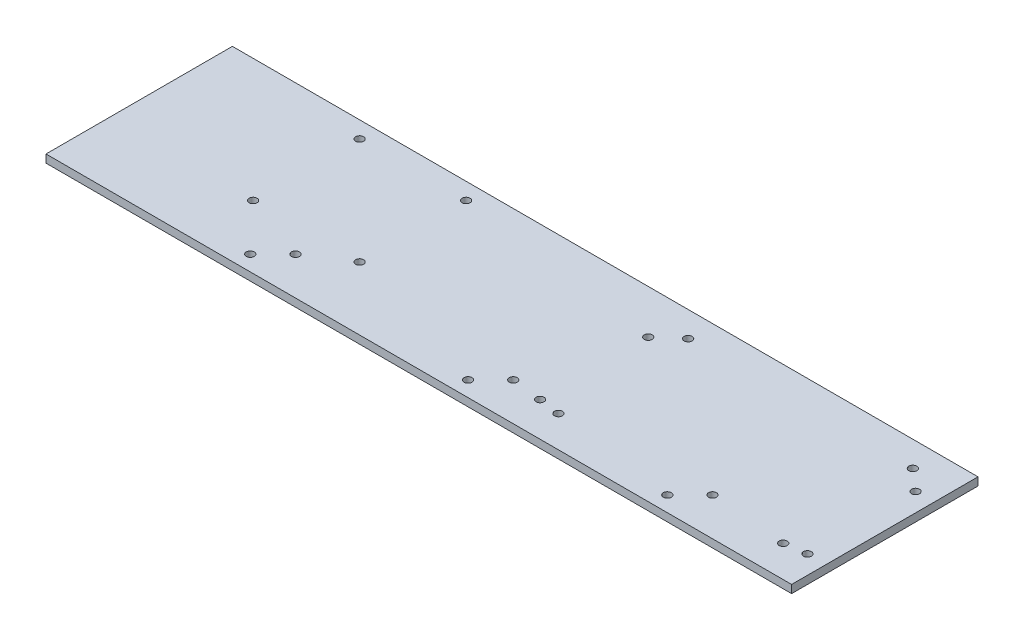
SolidWorks part; units mm, degrees
ref_plane "Front Plane" through (0, 0, 0) normal (0, 0, 1) x (1, 0, 0)
ref_plane "Top Plane" through (0, 0, 0) normal (0, 1, 0) x (1, 0, 0)
ref_plane "Right Plane" through (0, 0, 0) normal (1, 0, 0) x (0, 0, -1)
sketch "Sketch1" plane through (0, 0, 0) normal (0, 1, 0) x (1, 0, 0)
  line L1 (-140, -35) -> (140, -35)
  line L2 (-140, -35) -> (-140, 35)
  line L3 (-140, 35) -> (140, 35)
  line L4 (140, -35) -> (140, 35)
  line L5 (-140, -35) -> (140, 35) construction
  line L6 (-140, 35) -> (140, -35) construction
  circle A1 centre (87.5712, -29.2426) radius 1.5
  circle A2 centre (96.0565, -20.7574) radius 1.5
  circle A6 centre (133.0434, 18.5) radius 1.5 construction
  circle A9 centre (32.6434, 18.5) radius 1.5
  circle A10 centre (12.7294, -29.2426) radius 1.5
  circle A11 centre (21.2147, -20.7574) radius 1.5
  circle A12 centre (-60.5678, -20.7574) radius 1.5
  circle A13 centre (-69.0531, -29.2426) radius 1.5
  circle A14 centre (40.6434, 25.5) radius 1.5
  circle A15 centre (32.6434, -22.1) radius 1.5
  circle A16 centre (40.6434, -23.2) radius 1.5
  circle A17 centre (125.0434, -23.2) radius 1.5
  circle A18 centre (133.0434, -22.1) radius 1.5
  circle A19 centre (133.0434, 18.5) radius 1.5
  circle A20 centre (125.0434, 25.5) radius 1.5
  circle A21 centre (-85.9926, 28.7487) radius 1.5
  circle A22 centre (-45.9926, 28.7487) radius 1.5
  circle A23 centre (-45.9926, -11.2513) radius 1.5
  circle A24 centre (-85.9926, -11.2513) radius 1.5
  point P0 (0, 0)
  dimension "D3" = 3
  dimension "D4" = 3
  dimension "D5" = 3
  dimension "D6" = 3
  dimension "D7" = 3
  dimension "D8" = 3
  dimension "D9" = 3
  dimension "D10" = 3
  dimension "D11" = 3
  dimension "D12" = 3
  dimension "D13" = 3
  dimension "D14" = 3
  dimension "D15" = 3
  dimension "D1" = 280
  dimension "D2" = 70
extrude "Boss-Extrude1" add sketch "Sketch1" along normal blind 3
